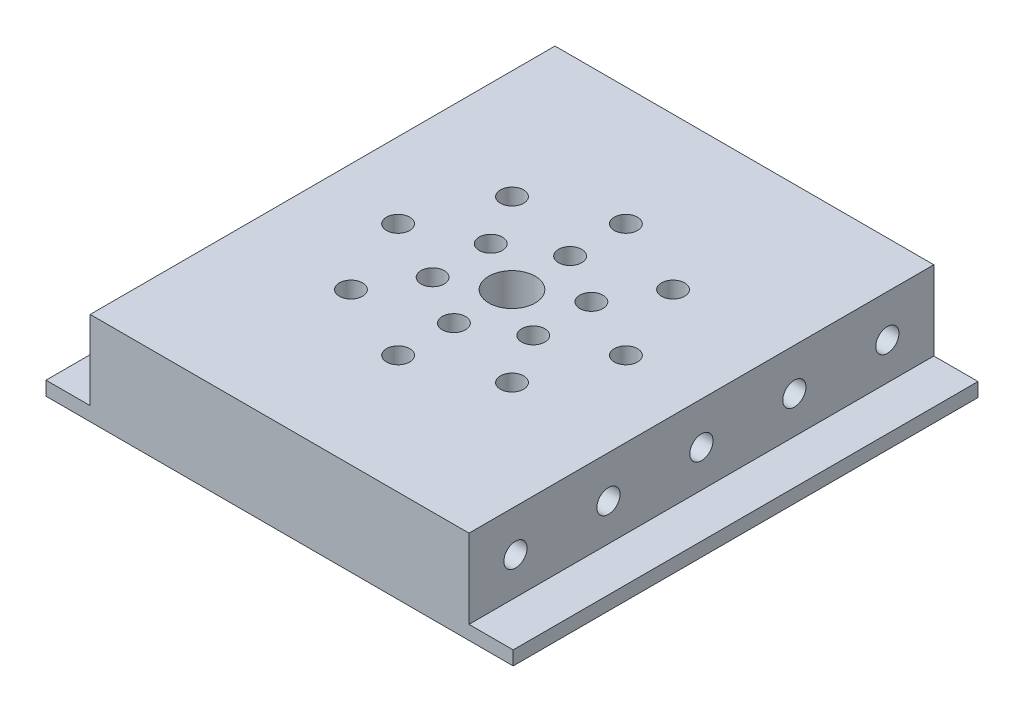
SolidWorks part; units mm, degrees
material "PVC rigide"
ref_plane "Plan de face" through (0, 0, 0) normal (0, 0, 1) x (1, 0, 0)
ref_plane "Plan de dessus" through (0, 0, 0) normal (0, 1, 0) x (1, 0, 0)
ref_plane "Plan de droite" through (0, 0, 0) normal (1, 0, 0) x (0, 0, -1)
sketch "Esquisse1" plane through (0, 0, 0) normal (0, 1, 0) x (1, 0, 0)
  line L1 (50.25, 50) -> (-50.25, 50)
  line L2 (50.25, 50) -> (50.25, -50)
  line L3 (50.25, -50) -> (-50.25, -50)
  line L4 (-50.25, 50) -> (-50.25, -50)
  line L5 (50.25, 50) -> (-50.25, -50) construction
  line L6 (50.25, -50) -> (-50.25, 50) construction
  point P0 (0, 0)
  dimension "D1" = 100.5
  dimension "D2" = 100
extrude "Boss.-Extru.1" add sketch "Esquisse1" along normal blind 20
sketch "Esquisse2" plane through (0, 20, 0) normal (0, 1, 0) x (1, 0, 0)
  line L0 (50.25, 50) -> (-50.25, 50) construction
  line L1 (50.25, -50) -> (40.75, -50)
  line L2 (50.25, -50) -> (50.25, 50)
  line L3 (50.25, 50) -> (40.75, 50)
  line L4 (40.75, -50) -> (40.75, 50)
  line L6 (-40.75, 50) -> (-50.25, 50)
  line L7 (-40.75, 50) -> (-40.75, -50)
  line L8 (-40.75, -50) -> (-50.25, -50)
  line L9 (-50.25, 50) -> (-50.25, -50)
  dimension "D1" = 9.5
extrude "Enlèv. mat.-Extru.1" cut sketch "Esquisse2" against normal offset from surface (17 mm away) 3 up to face at (0, 0, 0)
sketch "Esquisse3" plane through (-40.75, 0, 0) normal (-1, 0, 0) x (0, 0, 1)
  line L0 (-50, 11) -> (50, 11) construction
  line L1 (-50, 3) -> (-50, 20) construction
  line L2 (50, 3) -> (50, 20) construction
  line L3 (50, 3) -> (-50, 3) construction
  line L4 (0, 0) -> (0, 20) construction
  line L5 (50, 20) -> (-50, 20) construction
  circle A0 centre (-40, 11) radius 2.5
  circle A1 centre (-20, 11) radius 2.5
  circle A2 centre (0, 11) radius 2.5
  circle A3 centre (20, 11) radius 2.5
  circle A4 centre (40, 11) radius 2.5
  dimension "D4" = 5
  dimension "D1" = 8
  dimension "D2" = 10
  dimension "D3" = 20
extrude "Enlèv. mat.-Extru.2" cut sketch "Esquisse3" against normal blind 16
sketch "Esquisse4" plane through (40.75, 0, 0) normal (1, 0, 0) x (0, 0, -1)
  circle A1 centre (-20, 11) radius 2.5
  circle A2 centre (-20, 11) radius 2.5
  circle A3 centre (0, 11) radius 2.5
  circle A4 centre (0, 11) radius 2.5
  circle A5 centre (20, 11) radius 2.5
  circle A6 centre (20, 11) radius 2.5
  circle A7 centre (40, 11) radius 2.5
  circle A8 centre (40, 11) radius 2.5
  circle A9 centre (-40, 11) radius 2.5
  circle A10 centre (-40, 11) radius 2.5
  dimension "D1" = 0
  dimension "D2" = 0
  dimension "D3" = 0
  dimension "D4" = 0
  dimension "D5" = 0
extrude "Enlèv. mat.-Extru.3" cut sketch "Esquisse4" against normal blind 16
sketch "Esquisse5" plane through (0, 20, 0) normal (0, 1, 0) x (1, 0, 0)
  circle A0 centre (0, 0) radius 24.5 construction
  circle A1 centre (0, -24.5) radius 2.5
  circle A2 centre (-17.3241, -17.3241) radius 2.5
  circle A3 centre (-24.5, 0) radius 2.5
  circle A4 centre (-17.3241, 17.3241) radius 2.5
  circle A5 centre (0, 24.5) radius 2.5
  circle A6 centre (17.3241, 17.3241) radius 2.5
  circle A7 centre (24.5, 0) radius 2.5
  circle A8 centre (17.3241, -17.3241) radius 2.5
  dimension "D1" = 49
  dimension "D2" = 5
  dimension "D3" = 8
extrude "Enlèv. mat.-Extru.4" cut sketch "Esquisse5" against normal through all
sketch "Esquisse6" plane through (0, 20, 0) normal (0, 1, 0) x (1, 0, 0)
  circle A0 centre (0, 0) radius 5
  dimension "D1" = 10
extrude "Enlèv. mat.-Extru.5" cut sketch "Esquisse6" against normal through all
sketch "Esquisse7" plane through (0, 0, 0) normal (0, -1, 0) x (1, 0, 0)
  circle A0 centre (0, 0) radius 30
  dimension "D1" = 60
extrude "Enlèv. mat.-Extru.6" cut sketch "Esquisse7" against normal blind 4
sketch "Esquisse8" plane through (0, 4, 0) normal (0, -1, 0) x (1, 0, 0)
  circle A0 centre (0, 0) radius 19
  dimension "D1" = 38
extrude "Enlèv. mat.-Extru.7" cut sketch "Esquisse8" against normal blind 4
sketch "Esquisse9" plane through (0, 8, 0) normal (0, -1, 0) x (1, 0, 0)
  circle A0 centre (0, 0) radius 12.5 construction
  circle A1 centre (0, -12.5) radius 2.5
  circle A2 centre (-10.8253, -6.25) radius 2.5
  circle A3 centre (-10.8253, 6.25) radius 2.5
  circle A4 centre (0, 12.5) radius 2.5
  circle A5 centre (10.8253, 6.25) radius 2.5
  circle A6 centre (10.8253, -6.25) radius 2.5
  dimension "D1" = 25
  dimension "D2" = 5
  dimension "D3" = 6
extrude "Enlèv. mat.-Extru.8" cut sketch "Esquisse9" against normal through all
